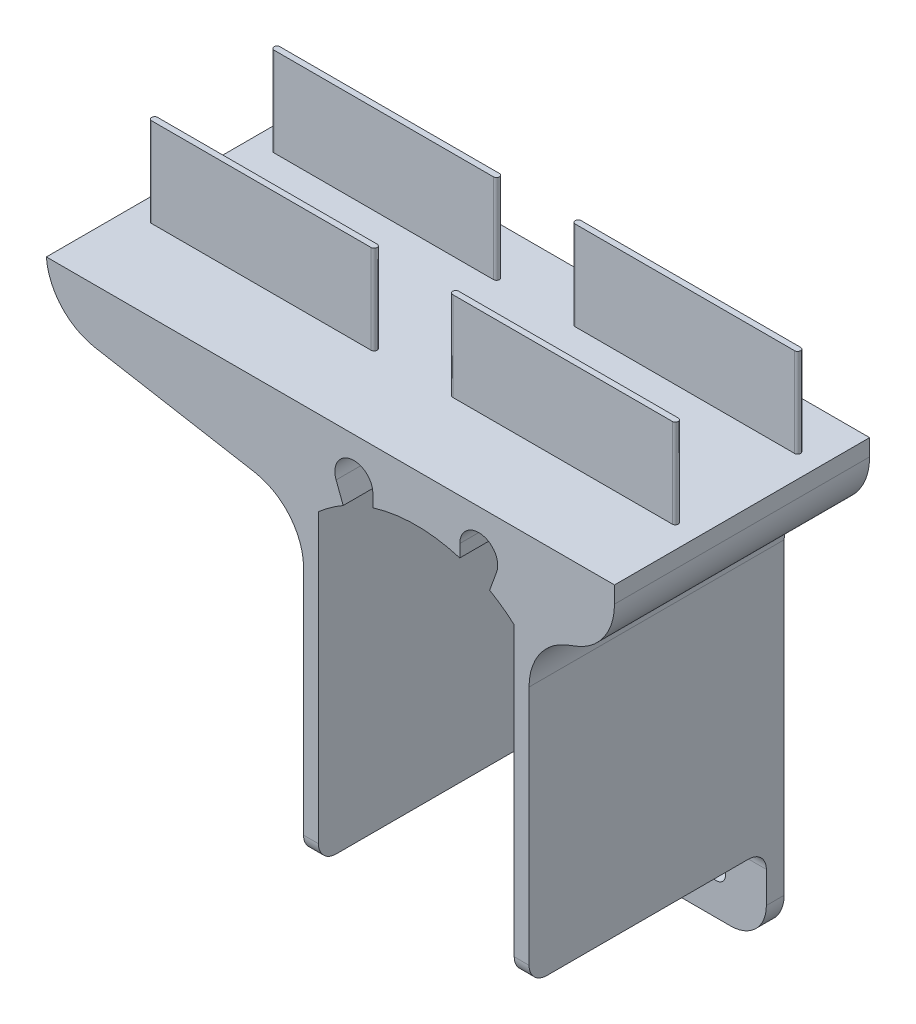
SolidWorks part; units mm, degrees
material "ABS"
ref_plane "Alzado" through (0, 0, 0) normal (0, 0, 1) x (1, 0, 0)
ref_plane "Planta" through (0, 0, 0) normal (0, 1, 0) x (1, 0, 0)
ref_plane "Vista lateral" through (0, 0, 0) normal (1, 0, 0) x (0, 0, -1)
sketch "Croquis4" plane through (0, 0, 0) normal (0, 0, 1) x (1, 0, 0)
  line L0 (-62.1753, -22.5138) -> (-62.1753, 45.4862)
  line L2 (-97.1753, -14.0138) -> (-97.1753, 36.9862) construction
  line L3 (-65.1753, 36.9862) -> (-65.1753, -14.0138) construction
  line L4 (-97.6753, -14.2397) -> (-97.6753, 37.2121)
  line L5 (-64.6753, 37.2121) -> (-64.6753, -14.2397)
  line L10 (-119.4893, 11.4862) -> (-39.0171, 11.4862) construction
  line L13 (-100.1753, -22.5138) -> (-100.1753, 45.4862)
  line L14 (-81.1753, 11.4862) -> (-81.1753, 55.3392) construction
  line L15 (-94.1753, 51.4862) -> (-68.1753, 51.4862)
  line L18 (-94.1753, -28.5138) -> (-68.1753, -28.5138)
  arc A0 (-62.1753, 45.4862) -> (-68.1753, 51.4862) centre (-68.1753, 45.4862) ccw
  arc A1 (-62.1753, -22.5138) -> (-68.1753, -28.5138) centre (-68.1753, -22.5138) cw
  arc A2 (-97.1753, -14.0138) -> (-65.1753, -14.0138) centre (-81.1753, 4.3195) ccw construction
  arc A3 (-65.1753, 36.9862) -> (-97.1753, 36.9862) centre (-81.1753, 18.6529) ccw construction
  arc A4 (-100.1753, -22.5138) -> (-94.1753, -28.5138) centre (-94.1753, -22.5138) ccw
  arc A8 (-68.6503, -23.214) -> (-72.6503, -23.214) centre (-70.6503, -21.5138) ccw construction
  arc A9 (-89.7003, -23.214) -> (-93.7003, -23.214) centre (-91.7003, -21.5138) ccw construction
  arc A10 (-93.7003, 46.1864) -> (-89.7003, 46.1864) centre (-91.7003, 44.4862) ccw construction
  arc A11 (-72.6503, 46.1864) -> (-68.6503, 46.1864) centre (-70.6503, 44.4862) ccw construction
  arc A12 (-64.6753, 37.2121) -> (-97.6753, 37.2121) centre (-81.1753, 18.6529) ccw
  arc A13 (-97.6753, -14.2397) -> (-64.6753, -14.2397) centre (-81.1753, 4.3195) ccw
  circle A14 centre (-91.7003, 44.4862) radius 1.6 construction
  circle A15 centre (-70.6503, 44.4862) radius 1.6 construction
  circle A16 centre (-91.7003, -21.5138) radius 1.6 construction
  circle A17 centre (-70.6503, -21.5138) radius 1.6 construction
  arc A20 (-100.1753, 45.4862) -> (-94.1753, 51.4862) centre (-94.1753, 45.4862) cw
  point P30 (-64.6753, 11.4862)
  point P39 (-81.1753, 51.4862)
  point P43 (-62.1753, 11.4862)
  point P48 (-100.1753, 11.4862)
  dimension "D2" = 3.2
  dimension "D3" = 6
  dimension "D4" = 2.5
  dimension "D5" = 40
  dimension "D1" = 0.5
extrude "Saliente-Extruir1" add sketch "Croquis4" along normal blind 3
sketch "Croquis5" plane through (0, 0, 3) normal (0, 0, 1) x (1, 0, 0)
  line L0 (-64.6753, -14.2397) -> (-64.6753, 37.2121) construction
  line L1 (-97.6753, 37.2121) -> (-97.6753, -14.2397) construction
  line L2 (-64.6753, -14.2397) -> (-64.6753, 37.2121)
  line L3 (-97.6753, 37.2121) -> (-97.6753, -14.2397)
  line L4 (-100.1753, 38.3026) -> (-100.1753, -14.2397)
  line L5 (-62.1753, -14.2397) -> (-62.1753, 38.3026)
  line L6 (-64.6753, -14.2397) -> (-62.1753, -14.2397)
  line L7 (-97.6753, -14.2397) -> (-100.1753, -14.2397)
  line L8 (-100.1753, 38.3026) -> (-100.1753, -15.3302) construction
  line L9 (-62.1753, -15.3302) -> (-62.1753, 38.3026) construction
  arc A1 (-64.6753, 37.2121) -> (-97.6753, 37.2121) centre (-81.1753, 18.6529) ccw construction
  arc A3 (-64.6753, 37.2121) -> (-97.6753, 37.2121) centre (-81.1753, 18.6529) ccw
  arc A4 (-62.1753, 38.3026) -> (-100.1753, 38.3026) centre (-81.1753, 18.6529) ccw
  arc A6 (-100.1753, -15.3302) -> (-62.1753, -15.3302) centre (-81.1753, 4.3195) ccw construction
  arc A7 (-97.6753, -14.2397) -> (-64.6753, -14.2397) centre (-81.1753, 4.3195) ccw construction
  dimension "D1" = 2.5
extrude "Saliente-Extruir2" add sketch "Croquis5" along normal blind 40
ref_plane "Plano1" through (0, 51.4862, 0) normal (0, -1, 0) x (-1, 0, 0)
sketch "Croquis6" plane through (0, 51.4862, 0) normal (0, -1, 0) x (-1, 0, 0)
  line L8 (49.7713, -7.6345) -> (49.7713, -8.6345) construction
  line L9 (88.7713, -6.6345) -> (50.7713, -6.6345) construction
  line L10 (89.7713, -8.6345) -> (89.7713, -7.6345) construction
  line L11 (50.7713, -9.6345) -> (88.7713, -9.6345) construction
  line L12 (49.7713, -28.2595) -> (49.7713, -29.2595)
  line L13 (88.7713, -27.2595) -> (50.7713, -27.2595)
  line L14 (89.7713, -29.2595) -> (89.7713, -28.2595)
  line L15 (50.7713, -30.2595) -> (88.7713, -30.2595)
  line L16 (49.7713, -28.2595) -> (49.7713, -29.2595) construction
  line L17 (88.7713, -27.2595) -> (50.7713, -27.2595) construction
  line L18 (89.7713, -29.2595) -> (89.7713, -28.2595) construction
  line L19 (50.7713, -30.2595) -> (88.7713, -30.2595) construction
  line L20 (141.5232, -29.2595) -> (141.5232, -28.2595)
  line L21 (102.5232, -30.2595) -> (140.5232, -30.2595)
  line L22 (101.5232, -28.2595) -> (101.5232, -29.2595)
  line L23 (140.5232, -27.2595) -> (102.5232, -27.2595)
  line L24 (141.5232, -29.2595) -> (141.5232, -28.2595) construction
  line L25 (102.5232, -30.2595) -> (140.5232, -30.2595) construction
  line L26 (101.5232, -28.2595) -> (101.5232, -29.2595) construction
  line L27 (140.5232, -27.2595) -> (102.5232, -27.2595) construction
  line L28 (141.5232, -8.6345) -> (141.5232, -7.6345)
  line L29 (102.5232, -9.6345) -> (140.5232, -9.6345)
  line L30 (101.5232, -7.6345) -> (101.5232, -8.6345)
  line L31 (140.5232, -6.6345) -> (102.5232, -6.6345)
  line L32 (141.5232, -8.6345) -> (141.5232, -7.6345) construction
  line L33 (102.5232, -9.6345) -> (140.5232, -9.6345) construction
  line L34 (101.5232, -7.6345) -> (101.5232, -8.6345) construction
  line L35 (140.5232, -6.6345) -> (102.5232, -6.6345) construction
  arc A8 (50.7713, -6.6345) -> (49.7713, -7.6345) centre (50.7713, -7.6345) ccw construction
  arc A9 (89.7713, -7.6345) -> (88.7713, -6.6345) centre (88.7713, -7.6345) ccw construction
  arc A10 (88.7713, -9.6345) -> (89.7713, -8.6345) centre (88.7713, -8.6345) ccw construction
  arc A11 (49.7713, -8.6345) -> (50.7713, -9.6345) centre (50.7713, -8.6345) ccw construction
  arc A12 (50.7713, -27.2595) -> (49.7713, -28.2595) centre (50.7713, -28.2595) ccw
  arc A13 (89.7713, -28.2595) -> (88.7713, -27.2595) centre (88.7713, -28.2595) ccw
  arc A14 (88.7713, -30.2595) -> (89.7713, -29.2595) centre (88.7713, -29.2595) ccw
  arc A15 (49.7713, -29.2595) -> (50.7713, -30.2595) centre (50.7713, -29.2595) ccw
  arc A16 (50.7713, -27.2595) -> (49.7713, -28.2595) centre (50.7713, -28.2595) ccw construction
  arc A17 (89.7713, -28.2595) -> (88.7713, -27.2595) centre (88.7713, -28.2595) ccw construction
  arc A18 (88.7713, -30.2595) -> (89.7713, -29.2595) centre (88.7713, -29.2595) ccw construction
  arc A19 (49.7713, -29.2595) -> (50.7713, -30.2595) centre (50.7713, -29.2595) ccw construction
  arc A20 (140.5232, -30.2595) -> (141.5232, -29.2595) centre (140.5232, -29.2595) ccw
  arc A21 (101.5232, -29.2595) -> (102.5232, -30.2595) centre (102.5232, -29.2595) ccw
  arc A22 (102.5232, -27.2595) -> (101.5232, -28.2595) centre (102.5232, -28.2595) ccw
  arc A23 (141.5232, -28.2595) -> (140.5232, -27.2595) centre (140.5232, -28.2595) ccw
  arc A24 (140.5232, -30.2595) -> (141.5232, -29.2595) centre (140.5232, -29.2595) ccw construction
  arc A25 (101.5232, -29.2595) -> (102.5232, -30.2595) centre (102.5232, -29.2595) ccw construction
  arc A26 (102.5232, -27.2595) -> (101.5232, -28.2595) centre (102.5232, -28.2595) ccw construction
  arc A27 (141.5232, -28.2595) -> (140.5232, -27.2595) centre (140.5232, -28.2595) ccw construction
  arc A28 (140.5232, -9.6345) -> (141.5232, -8.6345) centre (140.5232, -8.6345) ccw
  arc A29 (101.5232, -8.6345) -> (102.5232, -9.6345) centre (102.5232, -8.6345) ccw
  arc A30 (102.5232, -6.6345) -> (101.5232, -7.6345) centre (102.5232, -7.6345) ccw
  arc A31 (141.5232, -7.6345) -> (140.5232, -6.6345) centre (140.5232, -7.6345) ccw
  arc A32 (140.5232, -9.6345) -> (141.5232, -8.6345) centre (140.5232, -8.6345) ccw construction
  arc A33 (101.5232, -8.6345) -> (102.5232, -9.6345) centre (102.5232, -8.6345) ccw construction
  arc A34 (102.5232, -6.6345) -> (101.5232, -7.6345) centre (102.5232, -7.6345) ccw construction
  arc A35 (141.5232, -7.6345) -> (140.5232, -6.6345) centre (140.5232, -7.6345) ccw construction
  point P48 (0, 0)
  dimension "D2" = 0
  dimension "D3" = 0
  dimension "D4" = 0
ref_plane "Plano2" through (0, 0, 30.2595) normal (0, 0, 1) x (1, 0, 0)
sketch "Croquis7" plane through (0, 0, 30.2595) normal (0, 0, 1) x (1, 0, 0)
  line L0 (-141.5232, 51.4862) -> (-140.5232, 51.4862) construction
  line L1 (-50.7713, 51.4862) -> (-49.7713, 51.4862) construction
  line L2 (-141.5232, 51.4862) -> (-140.5232, 51.4862) construction
  line L3 (-50.7713, 51.4862) -> (-49.7713, 51.4862) construction
  line L4 (-143.5232, 51.4862) -> (-143.5232, 43.8023)
  line L5 (-62.1753, 45.4862) -> (-62.1753, 38.3026) construction
  line L6 (-100.1753, 38.3026) -> (-100.1753, 45.4862) construction
  line L7 (-62.1753, 45.4862) -> (-62.1753, 38.3026) construction
  line L8 (-100.1753, 38.3026) -> (-100.1753, 45.4862) construction
  line L9 (-143.5232, 43.8023) -> (-100.1753, 36.1589)
  line L10 (-47.7713, 51.4862) -> (-47.7713, 41.8929)
  line L11 (-47.7713, 41.8929) -> (-62.1753, 36.1589)
  line L13 (-143.5232, 51.4862) -> (-47.7713, 51.4862)
  line L14 (-100.1753, 36.1589) -> (-100.1753, 38.3026)
  line L15 (-62.1753, 36.1589) -> (-62.1753, 38.3026)
  arc A0 (-62.1753, 38.3026) -> (-100.1753, 38.3026) centre (-81.1753, 18.6529) ccw construction
  arc A1 (-62.1753, 38.3026) -> (-100.1753, 38.3026) centre (-81.1753, 18.6529) ccw
  dimension "D1" = 2
  dimension "D2" = 2
  dimension "D3" = 100
extrude "Saliente-Extruir3" add sketch "Croquis7" against normal up to surface (30.2595 mm away) from surface up to face at (-81.1753, 11.4862, 0) starting at face at (-81.1753, 13.5035, 43)
fillet "Redondeo1" radius 10 4 edges at (-62.1753, 36.1589, 21.5) (-47.7713, 41.8929, 21.5) (-143.5232, 43.8023, 21.5) (-100.1753, 36.1589, 21.5)
sketch "Croquis8" plane through (0, 51.4862, 0) normal (0, 1, 0) x (1, 0, 0)
  line L0 (-88.7713, -7.6345) -> (-51.7713, -7.6345)
  line L1 (-88.7713, -8.6345) -> (-51.7713, -8.6345)
  line L4 (-88.7713, -27.2595) -> (-50.7713, -27.2595) construction
  line L5 (-49.7713, -28.2595) -> (-49.7713, -29.2595) construction
  line L6 (-50.7713, -30.2595) -> (-88.7713, -30.2595) construction
  line L7 (-89.7713, -29.2595) -> (-89.7713, -28.2595) construction
  line L8 (-140.5232, -27.2595) -> (-102.5232, -27.2595) construction
  line L9 (-101.5232, -28.2595) -> (-101.5232, -29.2595) construction
  line L10 (-102.5232, -30.2595) -> (-140.5232, -30.2595) construction
  line L11 (-141.5232, -29.2595) -> (-141.5232, -28.2595) construction
  line L12 (-140.5232, -6.6345) -> (-102.5232, -6.6345) construction
  line L13 (-101.5232, -7.6345) -> (-101.5232, -8.6345) construction
  line L14 (-102.5232, -9.6345) -> (-140.5232, -9.6345) construction
  line L15 (-141.5232, -8.6345) -> (-141.5232, -7.6345) construction
  line L16 (-88.7713, -6.6345) -> (-50.7713, -6.6345) construction
  line L17 (-49.7713, -7.6345) -> (-49.7713, -8.6345) construction
  line L18 (-50.7713, -9.6345) -> (-88.7713, -9.6345) construction
  line L19 (-89.7713, -8.6345) -> (-89.7713, -7.6345) construction
  line L20 (-88.7713, -27.2595) -> (-50.7713, -27.2595) construction
  line L21 (-49.7713, -28.2595) -> (-49.7713, -29.2595) construction
  line L22 (-50.7713, -30.2595) -> (-88.7713, -30.2595) construction
  line L23 (-89.7713, -29.2595) -> (-89.7713, -28.2595) construction
  line L24 (-140.5232, -27.2595) -> (-102.5232, -27.2595) construction
  line L25 (-101.5232, -28.2595) -> (-101.5232, -29.2595) construction
  line L26 (-102.5232, -30.2595) -> (-140.5232, -30.2595) construction
  line L27 (-141.5232, -29.2595) -> (-141.5232, -28.2595) construction
  line L28 (-140.5232, -6.6345) -> (-102.5232, -6.6345) construction
  line L29 (-101.5232, -7.6345) -> (-101.5232, -8.6345) construction
  line L30 (-102.5232, -9.6345) -> (-140.5232, -9.6345) construction
  line L31 (-141.5232, -8.6345) -> (-141.5232, -7.6345) construction
  line L52 (-95.6473, 0) -> (-95.6473, -43) construction
  line L53 (-47.7713, 0) -> (-143.5232, 0) construction
  line L58 (-143.5232, -43) -> (-47.7713, -43) construction
  line L63 (-88.7713, -28.2595) -> (-51.7713, -28.2595)
  line L64 (-88.7713, -29.2595) -> (-51.7713, -29.2595)
  line L66 (-102.5232, -8.6345) -> (-139.5232, -8.6345)
  line L67 (-102.5232, -7.6345) -> (-139.5232, -7.6345)
  line L71 (-102.5232, -28.2595) -> (-139.5232, -28.2595)
  line L72 (-102.5232, -29.2595) -> (-139.5232, -29.2595)
  arc A0 (-88.7713, -8.6345) -> (-88.7713, -7.6345) centre (-88.7713, -8.1345) cw
  arc A1 (-51.7713, -7.6345) -> (-51.7713, -8.6345) centre (-51.7713, -8.1345) cw
  arc A4 (-49.7713, -28.2595) -> (-50.7713, -27.2595) centre (-50.7713, -28.2595) ccw construction
  arc A5 (-50.7713, -30.2595) -> (-49.7713, -29.2595) centre (-50.7713, -29.2595) ccw construction
  arc A6 (-89.7713, -29.2595) -> (-88.7713, -30.2595) centre (-88.7713, -29.2595) ccw construction
  arc A7 (-88.7713, -27.2595) -> (-89.7713, -28.2595) centre (-88.7713, -28.2595) ccw construction
  arc A8 (-101.5232, -28.2595) -> (-102.5232, -27.2595) centre (-102.5232, -28.2595) ccw construction
  arc A9 (-102.5232, -30.2595) -> (-101.5232, -29.2595) centre (-102.5232, -29.2595) ccw construction
  arc A10 (-141.5232, -29.2595) -> (-140.5232, -30.2595) centre (-140.5232, -29.2595) ccw construction
  arc A11 (-140.5232, -27.2595) -> (-141.5232, -28.2595) centre (-140.5232, -28.2595) ccw construction
  arc A12 (-101.5232, -7.6345) -> (-102.5232, -6.6345) centre (-102.5232, -7.6345) ccw construction
  arc A13 (-102.5232, -9.6345) -> (-101.5232, -8.6345) centre (-102.5232, -8.6345) ccw construction
  arc A14 (-141.5232, -8.6345) -> (-140.5232, -9.6345) centre (-140.5232, -8.6345) ccw construction
  arc A15 (-140.5232, -6.6345) -> (-141.5232, -7.6345) centre (-140.5232, -7.6345) ccw construction
  arc A16 (-49.7713, -7.6345) -> (-50.7713, -6.6345) centre (-50.7713, -7.6345) ccw construction
  arc A17 (-50.7713, -9.6345) -> (-49.7713, -8.6345) centre (-50.7713, -8.6345) ccw construction
  arc A18 (-89.7713, -8.6345) -> (-88.7713, -9.6345) centre (-88.7713, -8.6345) ccw construction
  arc A19 (-88.7713, -6.6345) -> (-89.7713, -7.6345) centre (-88.7713, -7.6345) ccw construction
  arc A20 (-49.7713, -28.2595) -> (-50.7713, -27.2595) centre (-50.7713, -28.2595) ccw construction
  arc A21 (-50.7713, -30.2595) -> (-49.7713, -29.2595) centre (-50.7713, -29.2595) ccw construction
  arc A22 (-89.7713, -29.2595) -> (-88.7713, -30.2595) centre (-88.7713, -29.2595) ccw construction
  arc A23 (-88.7713, -27.2595) -> (-89.7713, -28.2595) centre (-88.7713, -28.2595) ccw construction
  arc A24 (-101.5232, -28.2595) -> (-102.5232, -27.2595) centre (-102.5232, -28.2595) ccw construction
  arc A25 (-102.5232, -30.2595) -> (-101.5232, -29.2595) centre (-102.5232, -29.2595) ccw construction
  arc A26 (-141.5232, -29.2595) -> (-140.5232, -30.2595) centre (-140.5232, -29.2595) ccw construction
  arc A27 (-140.5232, -27.2595) -> (-141.5232, -28.2595) centre (-140.5232, -28.2595) ccw construction
  arc A28 (-101.5232, -7.6345) -> (-102.5232, -6.6345) centre (-102.5232, -7.6345) ccw construction
  arc A29 (-102.5232, -9.6345) -> (-101.5232, -8.6345) centre (-102.5232, -8.6345) ccw construction
  arc A30 (-141.5232, -8.6345) -> (-140.5232, -9.6345) centre (-140.5232, -8.6345) ccw construction
  arc A31 (-140.5232, -6.6345) -> (-141.5232, -7.6345) centre (-140.5232, -7.6345) ccw construction
  arc A32 (-102.5232, -8.6345) -> (-102.5232, -7.6345) centre (-102.5232, -8.1345) ccw
  arc A33 (-139.5232, -7.6345) -> (-139.5232, -8.6345) centre (-139.5232, -8.1345) ccw
  arc A34 (-102.5232, -28.2595) -> (-102.5232, -29.2595) centre (-102.5232, -28.7595) cw
  arc A35 (-139.5232, -29.2595) -> (-139.5232, -28.2595) centre (-139.5232, -28.7595) cw
  arc A36 (-51.7713, -29.2595) -> (-51.7713, -28.2595) centre (-51.7713, -28.7595) ccw
  arc A37 (-88.7713, -28.2595) -> (-88.7713, -29.2595) centre (-88.7713, -28.7595) ccw
  dimension "D1" = 37
extrude "Saliente-Extruir4" add sketch "Croquis8" along normal blind 15
sketch "Croquis9" plane through (0, 0, 0) normal (0, 0, -1) x (-1, 0, 0)
  circle A0 centre (91.7003, -21.5138) radius 1.6 construction
  circle A1 centre (70.6503, -21.5138) radius 1.6 construction
  circle A4 centre (91.7003, -21.5138) radius 1.6
  circle A5 centre (70.6503, -21.5138) radius 1.6
sketch "Croquis12" plane through (0, 0, 0) normal (0, 0, -1) x (-1, 0, 0)
  circle A0 centre (91.7003, -21.5138) radius 1.6 construction
  circle A1 centre (70.6503, -21.5138) radius 1.6 construction
  circle A2 centre (91.7003, -21.5138) radius 1.6
  circle A3 centre (70.6503, -21.5138) radius 1.6
  circle A4 centre (91.7003, 44.4862) radius 1.6 construction
  circle A5 centre (70.6503, 44.4862) radius 1.6 construction
  circle A6 centre (91.7003, 44.4862) radius 1.6
  circle A7 centre (70.6503, 44.4862) radius 1.6
extrude "Cortar-Extruir2" cut sketch "Croquis12" against normal blind 3
sketch "Croquis13" plane through (0, 0, 0) normal (0, 0, -1) x (-1, 0, 0)
  circle A0 centre (91.7003, 44.4862) radius 1.6 construction
  circle A1 centre (70.6503, 44.4862) radius 1.6 construction
  circle A2 centre (91.7003, 44.4862) radius 1.6 construction
  circle A3 centre (70.6503, 44.4862) radius 1.6 construction
  circle A4 centre (70.6503, 44.4862) radius 3.2
  circle A5 centre (91.7003, 44.4862) radius 3.2
  dimension "D1" = 6.4
extrude "Cortar-Extruir3" cut sketch "Croquis13" against normal through all from offset 3 offset against normal yes
fillet "Redondeo2" radius 3 4 edges at (-98.9253, -14.2397, 43) (-63.4253, -14.2397, 43) (-98.9253, -14.2397, 3) (-63.4253, -14.2397, 3)
sketch "Croquis14" plane through (0, 0, 43) normal (0, 0, 1) x (1, 0, 0)
  line L0 (-94.6911, 43.3481) -> (-92.3546, 37.2081)
  line L1 (-92.3546, 37.2081) -> (-88.5003, 37.2081)
  line L2 (-88.5003, 37.2081) -> (-88.5003, 44.4862)
  line L3 (-73.8503, 44.4862) -> (-73.8503, 37.2081)
  line L5 (-69.9105, 37.2081) -> (-67.6459, 43.3846)
  line L6 (-73.8503, 37.2081) -> (-69.9105, 37.2081)
  circle A0 centre (-70.6503, 44.4862) radius 3.2 construction
  circle A1 centre (-91.7003, 44.4862) radius 3.2 construction
  arc A2 (-67.6459, 43.3846) -> (-73.8503, 44.4862) centre (-70.6503, 44.4862) ccw
  arc A3 (-88.5003, 44.4862) -> (-94.6911, 43.3481) centre (-91.7003, 44.4862) ccw
  arc A4 (-91.3521, 41.3052) -> (-97.6753, 37.2121) centre (-81.1753, 18.6529) ccw construction
  arc A5 (-91.3521, 41.3052) -> (-97.6753, 37.2121) centre (-81.1753, 18.6529) ccw construction
extrude "Cortar-Extruir4" cut sketch "Croquis14" against normal up to surface (40 mm away) up to face at (-72.2503, 44.4862, 3)
